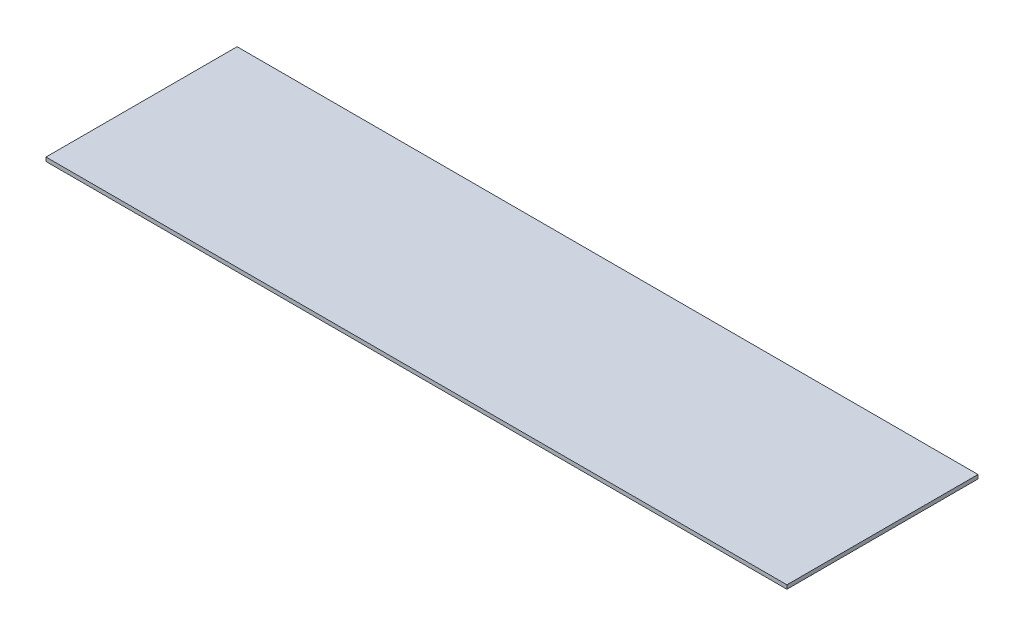
SolidWorks part; units mm, degrees
ref_plane "Ebene vorne" through (0, 0, 0) normal (0, 0, 1) x (1, 0, 0)
ref_plane "Ebene oben" through (0, 0, 0) normal (0, 1, 0) x (1, 0, 0)
ref_plane "Ebene rechts" through (0, 0, 0) normal (1, 0, 0) x (0, 0, -1)
sketch "Sketch1" plane through (0, 0, 0) normal (1, 0, 0) x (0, 0, -1)
  line L0 (0, 0) -> (0, 2)
  line L1 (0, 0) -> (98, 0)
  line L2 (98, 0) -> (98, 2)
  line L5 (0, 2) -> (98, 2)
  dimension "D4" = 2
  dimension "D5" = 98
extrude "Boss-Extrude1" add sketch "Sketch1" along normal blind 380
